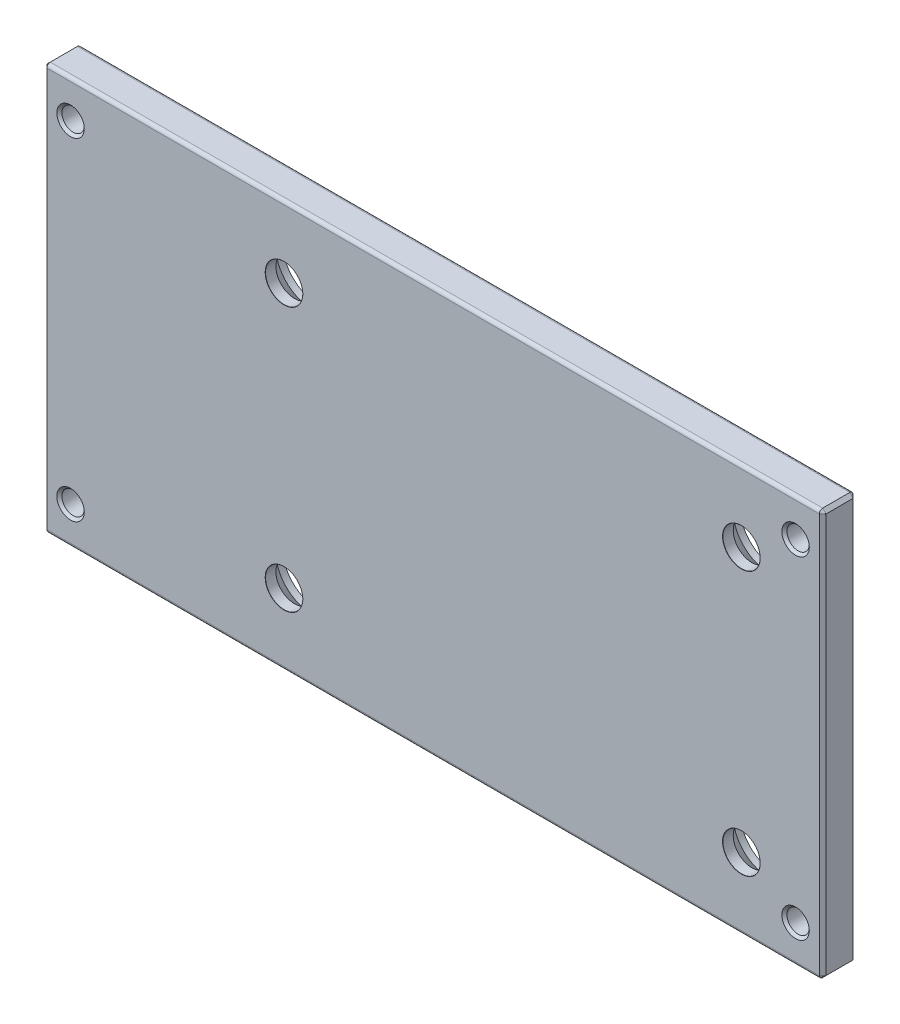
SolidWorks part; units mm, degrees
material "6061 Alloy"
ref_plane "Front Plane" through (0, 0, 0) normal (0, 0, 1) x (1, 0, 0)
ref_plane "Top Plane" through (0, 0, 0) normal (0, 1, 0) x (1, 0, 0)
ref_plane "Right Plane" through (0, 0, 0) normal (1, 0, 0) x (0, 0, -1)
sketch "Sketch1" plane through (0, 0, 0) normal (1, 0, 0) x (0, 0, -1)
  line L1 (-2.5, -30) -> (2.5, -30)
  line L2 (-2.5, -30) -> (-2.5, 30)
  line L3 (-2.5, 30) -> (2.5, 30)
  line L4 (2.5, -30) -> (2.5, 30)
  line L5 (-2.5, -30) -> (2.5, 30) construction
  line L6 (-2.5, 30) -> (2.5, -30) construction
  point P0 (0, 0)
  dimension "D1" = 5
  dimension "D2" = 60
extrude "Boss-Extrude1" add sketch "Sketch1" along normal mid plane 115
hole_wizard "M4 Tapped Hole1" positions "Sketch2" profile "Sketch3" tap size "M4" standard "ISO" end condition through all
sketch "Sketch2" plane through (0, 0, 2.5) normal (0, 0, 1) x (1, 0, 0)
  line L1 (-53.5, -24.5) -> (53.5, -24.5)
  line L2 (-53.5, -24.5) -> (-53.5, 24.5)
  line L3 (-53.5, 24.5) -> (53.5, 24.5)
  line L4 (53.5, -24.5) -> (53.5, 24.5)
  line L5 (-53.5, -24.5) -> (53.5, 24.5) construction
  line L6 (-53.5, 24.5) -> (53.5, -24.5) construction
  point P0 (-53.5, 24.5)
  point P2 (53.5, 24.5)
  point P4 (-53.5, -24.5)
  point P6 (53.5, -24.5)
  point P67 (0, 0)
  dimension "D1" = 107
  dimension "D2" = 49
sketch "Sketch3" plane through (-53.5, 24.5, 2.5) normal (1, 0, 0) x (0, -1, 0)
  line L0 (0, 0) -> (0, 5)
  line L1 (0, 5) -> (2.025, 5)
  line L2 (1.65, 4.625) -> (1.65, 0.375)
  line L3 (1.65, 0.375) -> (2.025, 0)
  line L5 (2.025, 0) -> (0, 0)
  line L6 (-1.65, 0.375) -> (-2.025, 0) construction
  line L7 (2.025, 5) -> (1.65, 4.625)
  line L8 (-2.025, 5) -> (-1.65, 4.625) construction
  line L11 (0, -6.35) -> (0, 107.95) construction
  dimension "Thru Tap Drill Dia." = 3.3
  dimension "Thru Tap Drill Depth" = 5
  dimension "Near C'Sink Dia." = 4.05
  dimension "Near C'Sink Angle" = 90
  dimension "Far C'Sink Dia." = 4.05
  dimension "Far C'Sink Angle" = 90
cosmetic thread "Hole Thread2" parameters "D2"=4
cosmetic thread "Hole Thread3" parameters "D2"=4
cosmetic thread "Hole Thread4" parameters "D2"=4
cosmetic thread "Hole Thread5" parameters "D2"=4
hole_wizard "CSK for M5 Countersunk Flat Head Screw1" positions "Sketch4" profile "Sketch6" countersink size "M5" standard "ISO" end condition through all
sketch "Sketch4" plane through (0, 0, -2.5) normal (0, 0, -1) x (-1, 0, 0)
  line L1 (-45.5, -19.5) -> (22, -19.5) construction
  line L2 (-45.5, -19.5) -> (-45.5, 19.5) construction
  line L3 (-45.5, 19.5) -> (22, 19.5) construction
  line L4 (22, -19.5) -> (22, 19.5) construction
  line L5 (-45.5, -19.5) -> (22, 19.5) construction
  line L6 (-45.5, 19.5) -> (22, -19.5) construction
  line L7 (-57.5, -30) -> (-57.5, 30) construction
  point P2 (22, 19.5)
  point P37 (-45.5, -19.5)
  point P38 (-45.5, 19.5)
  point P39 (22, -19.5)
  point P42 (-11.75, 0)
  dimension "D1" = 39
  dimension "D2" = 67.5
  dimension "D3" = 12
sketch "Sketch6" plane through (-22, 19.5, -2.5) normal (1, 0, 0) x (0, 1, 0)
  line L0 (0, 0) -> (0, 5)
  line L1 (0, 5) -> (2.775, 5)
  line L3 (2.75, 3.45) -> (5.2, 1)
  line L4 (5.2, 1) -> (5.2, 0)
  line L6 (5.2, 0) -> (0, 0)
  line L7 (-2.75, 3.45) -> (-5.2, 1) construction
  line L8 (2.775, 5) -> (2.75, 4.975)
  line L9 (2.75, 4.975) -> (2.75, 3.45)
  line L10 (-2.775, 5) -> (-2.75, 4.975) construction
  line L11 (0, -6.35) -> (0, 107.95) construction
  dimension "Thru Hole Dia." = 5.5
  dimension "Thru Hole Depth" = 5
  dimension "C'Sink Dia." = 10.4
  dimension "C'Sink Angle" = 90
  dimension "Far C'Sink Dia." = 5.55
  dimension "Far C'Sink Angle" = 90
  dimension "Head Clearance" = 1
fillet "Fillet1" radius 0.5 4 edges at (0, -30, -2.5) (0, -30, 2.5) (0, 30, -2.5) (0, 30, 2.5)
chamfer "Chamfer1" distance 0.5 angle 45 16 edges at (57.5, -29.8536, 2.3536) (57.5, 0, 2.5) (57.5, 29.8536, 2.3536) (57.5, 30, 0) (57.5, 29.8536, -2.3536) (57.5, 0, -2.5) (57.5, -29.8536, -2.3536) (57.5, -30, 0) (-57.5, 29.8536, -2.3536) (-57.5, 30, 0) (-57.5, 29.8536, 2.3536) (-57.5, 0, 2.5) (-57.5, -29.8536, 2.3536) (-57.5, -30, 0) (-57.5, -29.8536, -2.3536) (-57.5, 0, -2.5)
